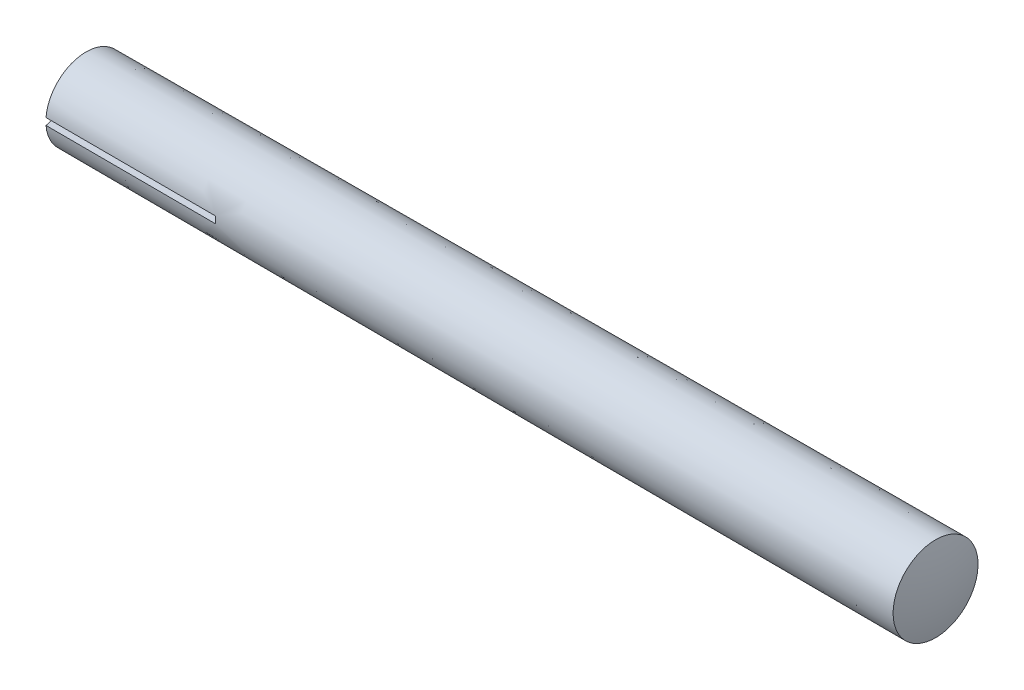
SolidWorks part; units mm, degrees
ref_plane "Front Plane" through (0, 0, 0) normal (0, 0, 1) x (1, 0, 0)
ref_plane "Top Plane" through (0, 0, 0) normal (0, 1, 0) x (1, 0, 0)
ref_plane "Right Plane" through (0, 0, 0) normal (1, 0, 0) x (0, 0, -1)
sketch "BodySke" plane through (0, 0, 0) normal (0, 0, 1) x (1, 0, 0)
  line L0 (-103.4174, 0) -> (209.4275, 0) construction
  line L1 (-0.3618, 0) -> (63.9033, 0)
  line L2 (0, 3.0096) -> (63.5, 3.175)
  line L3 (3.4925, 0) -> (-3.4925, 0) construction
  line L4 (0, 3.0096) -> (0, 0) construction
  line L5 (0, -3.4925) -> (0, 3.4925) construction
  arc A0 (0, 3.0096) -> (-0.3618, 0) centre (12.3382, 0) ccw
  arc A1 (63.5, 3.175) -> (63.9033, 0) centre (51.2033, 0) cw
  dimension "D4" = 12.7
  dimension "D5" = 12.7
  dimension "Diameter" = 6.35
  dimension "D2" = 6.0193
  dimension "Length" = 63.5
revolve "BaseBody" add sketch "BodySke" angle 360 about L0
ref_plane "Plane1" through (12.7, 0, 0) normal (1, 0, 0) x (0, 0, -1)
sketch "SplSke" plane through (0, 0, 0) normal (1, 0, 0) x (0, 0, -1)
  line L0 (6.35, 0.254) -> (6.35, -0.254)
  line L1 (6.35, 0.254) -> (-6.35, 0.254)
  line L2 (-6.35, 0.254) -> (-6.35, -0.254)
  line L3 (6.35, -0.254) -> (-6.35, -0.254)
  line L4 (3.4925, 0) -> (-3.4925, 0) construction
  line L5 (0, 0) -> (0, 5.953) construction
  dimension "D1" = 12.7
  dimension "D2" = 0.254
extrude "Split" cut sketch "SplSke" along normal up to surface (12.7 mm away) and the other way through all up to plane "Plane1"
equation "\"D4@BodySke\" = \"Diameter@BodySke\"*2"
equation "\"D5@BodySke\" = \"Diameter@BodySke\" * 2"
equation "\"D2@BodySke\" = \"Diameter@BodySke\"-\"Diameter@BodySke\" * \"Length@BodySke\" / 48"
equation "\"D1@Plane1\"=\"Length@BodySke\"*0.2"
equation "\"D2@SplSke\" = \"Split_Width@SplSke\"/2"
equation "\"D1@SplSke\"=\"Diameter@BodySke\" * 2"
